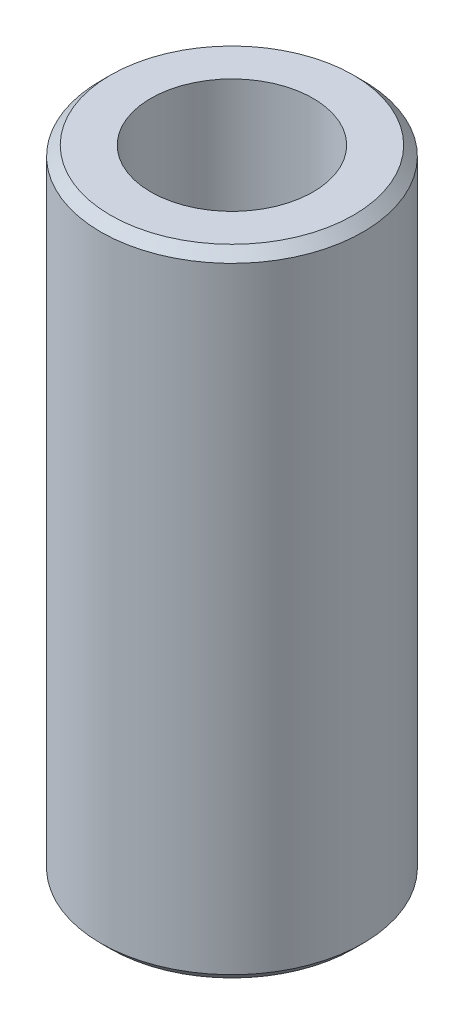
SolidWorks part; units mm, degrees
ref_plane "Front Plane" through (0, 0, 0) normal (0, 0, 1) x (1, 0, 0)
ref_plane "Top Plane" through (0, 0, 0) normal (0, 1, 0) x (1, 0, 0)
ref_plane "Right Plane" through (0, 0, 0) normal (1, 0, 0) x (0, 0, -1)
sketch "Sketch1" plane through (0, 0, 0) normal (0, 1, 0) x (1, 0, 0)
  circle A0 centre (0, 0) radius 47.5
  dimension "SHAFT_OD" = 95
extrude "Boss-Extrude1" add sketch "Sketch1" along normal blind 230.1845
sketch "Sketch2" plane through (0, 0, 0) normal (0, 1, 0) x (1, 0, 0)
  circle A0 centre (0, 0) radius 29.3982
  dimension "BORE_D" = 58.7963
extrude "Cut-Extrude1" cut sketch "Sketch2" along normal through all
chamfer "Chamfer1" distance 3.5074 angle 45 2 edges at (0, 230.1845, 47.5) (0, 0, 47.5)
